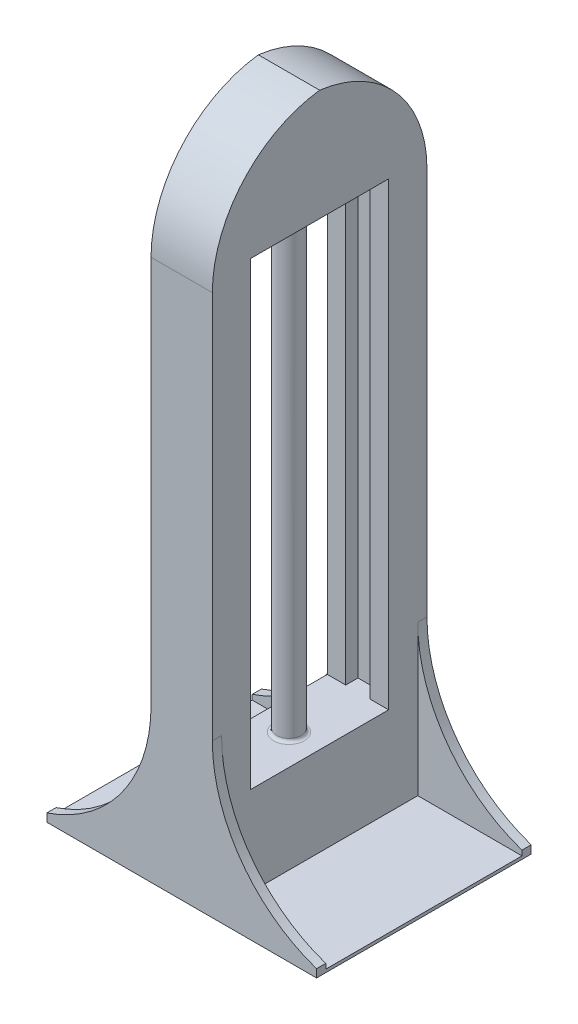
SolidWorks part; units mm, degrees
material "6061-T6 (SS)"
ref_plane "Ebene vorne" through (0, 0, 0) normal (0, 0, 1) x (1, 0, 0)
ref_plane "Ebene oben" through (0, 0, 0) normal (0, 1, 0) x (1, 0, 0)
ref_plane "Ebene rechts" through (0, 0, 0) normal (1, 0, 0) x (0, 0, -1)
sketch "Skizze1" plane through (0, 0, 0) normal (0, 0, 1) x (1, 0, 0)
  line L1 (-100, 0) -> (100, 0)
  line L2 (-100, 0) -> (-100, 2166)
  line L3 (-100, 2166) -> (100, 2166)
  line L4 (100, 0) -> (100, 2166)
  dimension "D1" = 2166
  dimension "D2" = 100
  dimension "D3" = 100
extrude "Aufsatz-Linear austragen1" add sketch "Skizze1" along normal blind 350 and the other way blind 350
fillet "Verrundung1" radius 400 2 edges at (0, 2166, -350) (0, 2166, 350)
sketch "Skizze2" plane through (100, 0, 0) normal (1, 0, 0) x (0, 0, -1)
  line L0 (350, 0) -> (-350, 0) construction
  line L1 (-225, 300) -> (225, 300)
  line L2 (-225, 300) -> (-225, 1800)
  line L3 (-225, 1800) -> (225, 1800)
  line L4 (225, 300) -> (225, 1800)
  line L5 (-225, 300) -> (225, 1800) construction
  line L6 (-225, 1800) -> (225, 300) construction
  point P0 (0, 1050)
  point P7 (0, 300)
  dimension "D1" = 300
  dimension "D2" = 1500
  dimension "D3" = 450
extrude "Schnitt-Linear austragen1" cut sketch "Skizze2" against normal up to surface (200 mm away) up to face at (-100, 1165.4301, 0)
sketch "Skizze4" plane through (0, 0, -225) normal (0, 0, 1) x (1, 0, 0)
  line L0 (-100, 1800) -> (100, 1800) construction
  line L1 (-40, 1800) -> (40, 1800)
  line L2 (-40, 1800) -> (-40, 300)
  line L3 (-40, 300) -> (40, 300)
  line L4 (40, 1800) -> (40, 300)
  line L5 (-100, 300) -> (100, 300) construction
  line L6 (0, 1800) -> (0, 1438.3891) construction
  point P8 (0, 1800)
  dimension "D1" = 80
extrude "Schnitt-Linear austragen2" cut sketch "Skizze4" against normal blind 40
mirror "Spiegeln1" about plane through (0, 0, 0) normal (0, 0, 1) of "Schnitt-Linear austragen2"
sketch "Skizze5" plane through (0, 300, 0) normal (0, 1, 0) x (1, 0, 0)
  circle A0 centre (0, 0) radius 40
  dimension "D1" = 80
extrude "Aufsatz-Linear austragen2" add sketch "Skizze5" along normal up to surface (1500 mm away) up to face at (0, 1800, 0)
fillet "Verrundung2" radius 10 2 edges at (0, 1800, 40) (0, 300, -40)
sketch "Skizze6" plane through (100, 0, 0) normal (1, 0, 0) x (0, 0, -1)
  line L0 (0, 0) -> (0, 452.5048) construction
  line L1 (-350, 0) -> (-320, 0)
  line L2 (-350, 0) -> (-350, 500)
  line L3 (-350, 500) -> (-320, 500)
  line L4 (-320, 0) -> (-320, 500)
  line L5 (350, 0) -> (320, 0)
  line L6 (320, 0) -> (320, 500)
  line L7 (350, 0) -> (350, 500)
  line L8 (350, 500) -> (320, 500)
  dimension "D1" = 500
  dimension "D2" = 30
extrude "Aufsatz-Linear austragen3" add sketch "Skizze6" along normal blind 500
mirror "Spiegeln2" about plane through (0, 0, 0) normal (1, 0, 0) of "Aufsatz-Linear austragen3"
sketch "Skizze7" plane through (0, 0, 0) normal (0, -1, 0) x (1, 0, 0)
  line L1 (-600, -350) -> (600, -350)
  line L2 (-600, -350) -> (-600, 350)
  line L3 (-600, 350) -> (600, 350)
  line L4 (600, -350) -> (600, 350)
extrude "Aufsatz-Linear austragen4" add sketch "Skizze7" against normal blind 10
sketch "Skizze9" plane through (0, 0, 350) normal (0, 0, 1) x (1, 0, 0)
  line L0 (600, 500) -> (600, 0) construction
  arc A0 (100, 500) -> (600, 0) centre (600, 500) ccw
extrude "Schnitt-Linear austragen3" cut sketch "Skizze9" against normal through all and the other way through all
mirror "Spiegeln3" about plane through (0, 0, 0) normal (1, 0, 0) of "Schnitt-Linear austragen3"
sketch "Skizze10" plane through (0, 10, 0) normal (0, 1, 0) x (1, 0, 0)
  line L0 (100, -350) -> (600, -350) construction
  line L1 (600, 350) -> (440, 350)
  line L2 (600, 350) -> (600, -350)
  line L3 (600, -350) -> (440, -350)
  line L4 (440, 350) -> (440, -350)
  dimension "D1" = 160
extrude "Schnitt-Linear austragen4" cut sketch "Skizze10" against normal up to surface (10 mm away) and the other way through all up to face at (0, 0, 0)
mirror "Spiegeln4" about plane through (0, 0, 0) normal (1, 0, 0) of "Schnitt-Linear austragen4"
